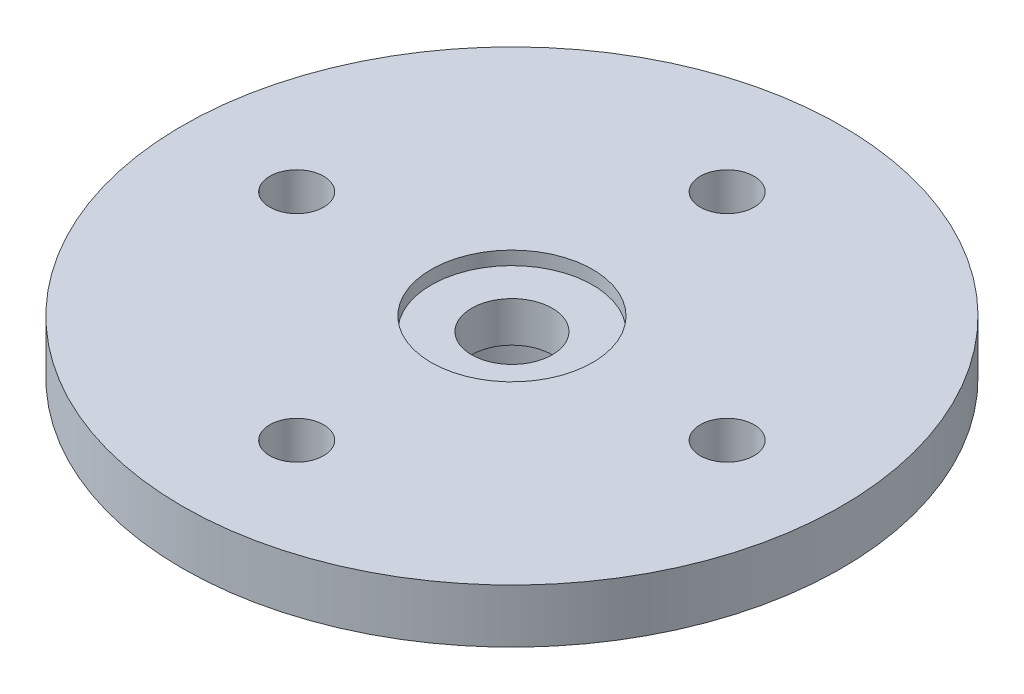
SolidWorks part; units mm, degrees
ref_plane "前视基准面" through (0, 0, 0) normal (0, 0, 1) x (1, 0, 0)
ref_plane "上视基准面" through (0, 0, 0) normal (0, 1, 0) x (1, 0, 0)
ref_plane "右视基准面" through (0, 0, 0) normal (1, 0, 0) x (0, 0, -1)
sketch "草图1" plane through (0, 0, 0) normal (0, 1, 0) x (1, 0, 0)
  circle A0 centre (0, 0) radius 12.25
  circle A1 centre (0, 0) radius 8 construction
  circle A2 centre (0, 8) radius 1
  circle A3 centre (8, 0) radius 1
  circle A4 centre (0, -8) radius 1
  circle A5 centre (-8, 0) radius 1
  circle A6 centre (0, 0) radius 3
  circle A7 centre (0, 0) radius 2.9
  circle A8 centre (0, 0) radius 1.5
  point P15 (0, 0)
  dimension "D1" = 24.5
  dimension "D2" = 4
extrude "凸台-拉伸1" add sketch "草图1" along normal blind 2 contours A0 A6 A5 A4 A3 A2 | A6 A7 | A7 A8 region at (-11.9035, 0, 0) region at (-2.9151, 0, 0) region at (-2.818, 0, 0)
sketch "草图2" plane through (0, 0, 0) normal (0, -1, 0) x (1, 0, 0)
  circle A0 centre (0, 0) radius 2.9
  circle A1 centre (0, 0) radius 4.9
extrude "凸台-拉伸2" add sketch "草图2" along normal blind 3
extrude "切除-拉伸1" cut sketch "草图1<4>" against normal blind 0.5 from surface contours A6 starting at face at (-8, 2, 1)
sketch "草图1<4>" plane through (0, 0, 0) normal (0, 1, 0) x (1, 0, 0) same geometry as "草图1"
